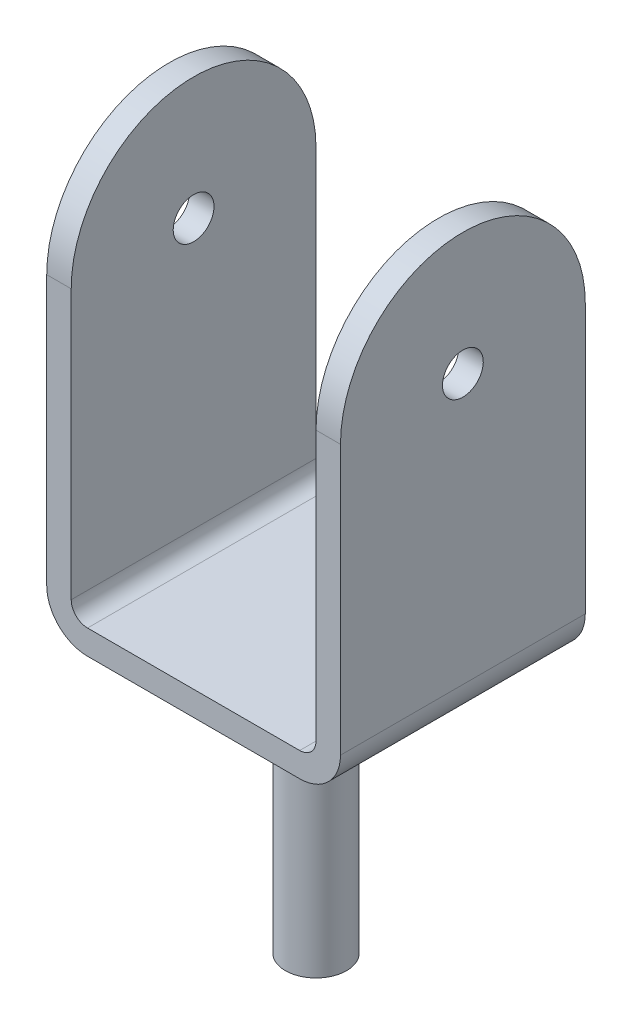
SolidWorks part; units mm, degrees
ref_plane "Front Plane" through (0, 0, 0) normal (0, 0, 1) x (1, 0, 0)
ref_plane "Top Plane" through (0, 0, 0) normal (0, 1, 0) x (1, 0, 0)
ref_plane "Right Plane" through (0, 0, 0) normal (1, 0, 0) x (0, 0, -1)
sketch "Sketch1" plane through (0, 0, 0) normal (0, 0, 1) x (1, 0, 0)
  line L0 (-130, 0) -> (130, 0)
  line L1 (180, 50) -> (180, 380)
  line L2 (180, 380) -> (150, 380)
  line L3 (150, 380) -> (150, 50)
  line L4 (130, 30) -> (-130, 30)
  line L5 (-150, 50) -> (-150, 380)
  line L6 (-150, 380) -> (-180, 380)
  line L7 (-180, 380) -> (-180, 50)
  line L8 (0, 178.2732) -> (0, -178.2732) construction
  arc A0 (-130, 30) -> (-150, 50) centre (-130, 50) cw
  arc A1 (130, 30) -> (150, 50) centre (130, 50) ccw
  arc A2 (130, 0) -> (180, 50) centre (130, 50) ccw
  arc A3 (-130, 0) -> (-180, 50) centre (-130, 50) cw
  point P4 (0, 0)
  point P12 (0, 178.2732)
  point P15 (0, 0)
  dimension "D6" = 20
  dimension "D7" = 20
  dimension "D8" = 50
  dimension "D1" = 360
  dimension "D2" = 30
  dimension "D3" = 30
  dimension "D4" = 30
  dimension "D5" = 380
extrude "Boss-Extrude1" add sketch "Sketch1" along normal blind 300
sketch "Sketch2" plane through (0, 0, 0) normal (0, -1, 0) x (1, 0, 0)
  line L0 (-130, 0) -> (130, 0) construction
  line L1 (180, 300) -> (180, 0) construction
  circle A0 centre (0, 150) radius 37.5
  dimension "D1" = 75
  dimension "D2" = 150
  dimension "D3" = 180
extrude "Boss-Extrude2" add sketch "Sketch2" along normal blind 325 contours A0
sketch "Sketch3" plane through (180, 0, 0) normal (1, 0, 0) x (0, 0, -1)
  line L0 (-300, 50) -> (-300, 380) construction
  line L1 (0, 50) -> (0, 380) construction
  arc A0 (-300, 380) -> (0, 380) centre (-150, 380) cw
  circle A1 centre (-150, 380) radius 25
  line M2 (0, 380) -> (-300, 380)
  dimension "D1" = 50
extrude "Boss-Extrude3" add sketch "Sketch3" against normal up to surface (30 mm away) contours A1 A0 M2 region at (180, 445.1777, 150) up to face at (150, 215, 150)
extrude "Cut-Extrude1" cut sketch "Sketch3<4>" against normal up to surface (360 mm away) contours A1 up to face at (-180, 215, 150)
sketch "Sketch3<4>" plane through (180, 0, 0) normal (1, 0, 0) x (0, 0, -1) same geometry as "Sketch3"
sketch "Sketch6" plane through (-180, 0, 0) normal (-1, 0, 0) x (0, 0, 1)
  line L0 (0, 380) -> (0, 50) construction
  line L1 (300, 380) -> (300, 50) construction
  line L7 (300, 380) -> (175, 380)
  line L8 (125, 380) -> (0, 380)
  line L9 (0, 380) -> (0, 50)
  line L10 (0, 50) -> (300, 50)
  line L11 (300, 50) -> (300, 380)
  line L14 (0, 380) -> (0, 50)
  line L15 (0, 50) -> (300, 50)
  line L16 (300, 50) -> (300, 380)
  arc A0 (0, 380) -> (300, 380) centre (150, 380) cw
  arc A2 (125, 380) -> (175, 380) centre (150, 380) ccw
  point P3 (-809.8843, 167.5668)
  dimension "D1" = 0
extrude "Boss-Extrude4" add sketch "Sketch6" against normal up to surface (30 mm away) up to face at (-150, 265.8333, 150)
extrude "Cut-Extrude2" cut sketch "Sketch3<9>" against normal up to surface (360 mm away) contours A1 up to face at (-180, 252.5, 150)
sketch "Sketch3<9>" plane through (180, 0, 0) normal (1, 0, 0) x (0, 0, -1) same geometry as "Sketch3"
